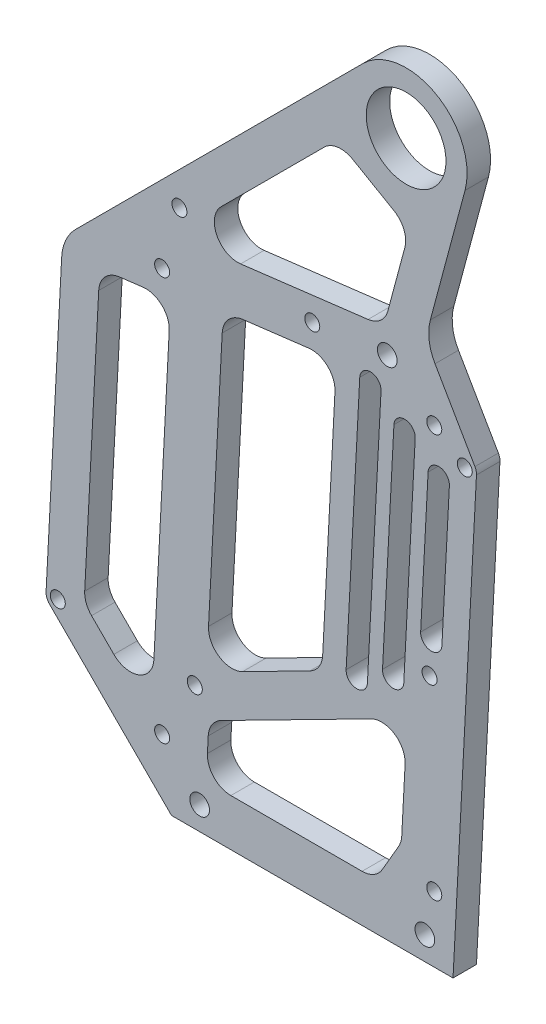
SolidWorks part; units mm, degrees
material "6061 Alloy"
ref_plane "Front Plane" through (0, 0, 0) normal (0, 0, 1) x (1, 0, 0)
ref_plane "Top Plane" through (0, 0, 0) normal (0, 1, 0) x (1, 0, 0)
ref_plane "Right Plane" through (0, 0, 0) normal (1, 0, 0) x (0, 0, -1)
sketch "Sketch1" plane through (0, 0, 0) normal (0, 0, 1) x (1, 0, 0)
  line L0 (0, 103.759) -> (0, -103.759) construction
  line L1 (-30, 76) -> (50, 76)
  line L2 (-30, 76) -> (-30, 256)
  line L3 (-30, 256) -> (50, 256)
  line L4 (50, 76) -> (50, 256)
  circle A0 centre (20, 226) radius 8.5
  dimension "D1" = 150
  dimension "D5" = 17
  dimension "D2" = 20
  dimension "D3" = 180
  dimension "D4" = 80
extrude "Boss-Extrude1" add sketch "Sketch1" along normal blind 5
sketch "Sketch2" plane through (0, 0, 5) normal (0, 0, 1) x (1, 0, 0)
  line L0 (20, 226) -> (20, 151) construction
  line L1 (20, 226) -> (-17.1819, 226) construction
  circle A0 centre (20, 151) radius 5.5
  dimension "D3" = 11
  dimension "D1" = 75
  dimension "D2" = 90
extrude "Cut-Extrude1" cut sketch "Sketch2" against normal blind 30
sketch "Sketch3" plane through (0, 0, 5) normal (0, 0, 1) x (1, 0, 0)
  circle A0 centre (0, 182) radius 1.6
  circle A1 centre (25, 129.3013) radius 1.6
  circle A2 centre (-25.0329, 102.5335) radius 1.6
  circle A3 centre (-15, 81) radius 2.5
  circle A4 centre (15, 81) radius 2.5
  circle A5 centre (24, 91) radius 2.5
  circle A6 centre (-24, 91) radius 2.5
  dimension "D1" = 5
  dimension "D2" = 3.2
extrude "Cut-Extrude2" cut sketch "Sketch3" against normal blind 5
sketch "Sketch4" plane through (0, 0, 5) normal (0, 0, 1) x (1, 0, 0)
  line L0 (10.8076, 235.1924) -> (-46.0411, 178.3437)
  line L1 (-46.0411, 178.3437) -> (-46.0411, 109.8941)
  line L2 (-46.0411, 109.8941) -> (-30, 76)
  line L3 (32.557, 222.6354) -> (22.7869, 186.1729)
  line L4 (22.7869, 186.1729) -> (30, 173.6795)
  line L5 (30, 173.6795) -> (30, 76)
  line L6 (-30, 76) -> (50, 76) construction
  line L7 (30, 76) -> (50, 76)
  line L8 (50, 76) -> (50, 256)
  line L9 (50, 256) -> (-30, 256)
  line L10 (-30, 256) -> (-68.6435, 166)
  line L11 (-68.6435, 166) -> (-57.2516, 84.4416)
  line L12 (-57.2516, 84.4416) -> (-30, 76)
  circle A0 centre (20, 226) radius 13
  circle A1 centre (20, 151) radius 5.5 construction
  line M14 (-30, 256) -> (-30, 76)
  line M15 (-30, 76) -> (50, 76)
  line M16 (50, 76) -> (50, 256)
  line M17 (50, 256) -> (-30, 256)
  dimension "D1" = 26
  dimension "D4" = 20
  dimension "D5" = 60
  dimension "D2" = 75
  dimension "D3" = 45
  dimension "D6" = 60
extrude "Cut-Extrude3" cut sketch "Sketch4" against normal blind 10 contours A0 L3 L4 L5 L0 M15 M16 M17 M14 region at (-10.989, 216.1814, 5)
sketch "Sketch5" plane through (0, 0, 5) normal (0, 0, 1) x (1, 0, 0)
  line L0 (-30, 194.3848) -> (-46.5355, 177.8492)
  line L1 (-48, 174.3137) -> (-48, 96.0711)
  line L2 (-46.5355, 92.5355) -> (-30, 76)
  line L4 (10.8076, 235.1924) -> (-30, 194.3848) construction
  line L6 (-30, 194.3848) -> (-30, 76) construction
  line L15 (-30, 76) -> (30, 76) construction
  line L16 (-35, 169.3848) -> (-35, 101) construction
  line L17 (-30, 169.3848) -> (-30, 101)
  line L18 (-40, 169.3848) -> (-40, 101)
  line L19 (-30, 138.6777) -> (-30, 121.7071)
  line L20 (-30, 138.6777) -> (-40, 148.6777)
  line L21 (-30, 121.7071) -> (-40, 131.7071)
  line L22 (-40, 148.6777) -> (-40, 131.7071)
  line L23 (-40, 148.6777) -> (-30, 121.7071)
  arc A0 (-30, 169.3848) -> (-40, 169.3848) centre (-35, 169.3848) ccw
  arc A1 (-40, 101) -> (-30, 101) centre (-35, 101) ccw
  arc A2 (-48, 96.0711) -> (-46.5355, 92.5355) centre (-43, 96.0711) ccw
  arc A3 (-46.5355, 177.8492) -> (-48, 174.3137) centre (-43, 174.3137) ccw
  point P14 (-35, 135.1924)
  point P26 (-48, 94)
  point P29 (-48, 176.3848)
  line M19 (-30, 194.3848) -> (-30, 76)
  dimension "D6" = 5
  dimension "D9" = 5
  dimension "D1" = 18
  dimension "D2" = 45
  dimension "D3" = 7
  dimension "D4" = 7
  dimension "D5" = 8
  dimension "D7" = 12
  dimension "D8" = 135
extrude "Boss-Extrude2" add sketch "Sketch5" against normal blind 5 contours L1 L2 L0 A1 L18 A0 L17 M19 | L16 L23 L18 L21 | L20 L16 L23 L17 | L16 L20 L23 | L23 L16 L21 region at (-40.982, 135.1924, 5) region at (-32.2222, 134.3002, 5) region at (-33.3333, 127.8689, 5) region at (-36.6667, 142.5159, 5) region at (-37.7778, 136.0845, 5)
fillet "Fillet1" radius 2 4 edges at (-40, 131.7071, 2.5) (-40, 148.6777, 2.5) (-30, 121.7071, 2.5) (-30, 138.6777, 2.5)
fillet "Fillet2" radius 5 2 edges at (30, 173.6795, 2.5) (22.7869, 186.1729, 2.5)
sketch "Sketch6" plane through (0, 0, 5) normal (0, 0, 1) x (1, 0, 0)
  line L0 (32.557, 222.6354) -> (23.323, 188.1734) construction
  line L1 (23.8225, 184.3793) -> (29.3301, 174.8397) construction
  circle A0 centre (15.9821, 183.9592) radius 2.1
  dimension "D1" = 4.2
  dimension "D2" = 6
  dimension "D3" = 7
extrude "Cut-Extrude4" cut sketch "Sketch6" against normal blind 5
sketch "Sketch7" plane through (0, 0, 0) normal (0, 0, -1) x (-1, 0, 0)
  line L1 (-30, 76) -> (28.3649, 76)
  line L2 (-30, 76) -> (-30, 95.1786)
  line L3 (-30, 95.1786) -> (28.3649, 95.1786)
  line L4 (28.3649, 76) -> (28.3649, 95.1786)
extrude "Boss-Extrude3" add sketch "Sketch7" against normal blind 5
sketch "Sketch8" plane through (0, 0, 0) normal (0, 0, -1) x (-1, 0, 0)
  circle A0 centre (24, 81) radius 2.1
  circle A1 centre (-24, 81) radius 2.1
extrude "Cut-Extrude5" cut sketch "Sketch8" against normal blind 5
sketch "Sketch9" plane through (0, 0, 0) normal (0, 0, -1) x (-1, 0, 0)
  circle A0 centre (-26, 176) radius 1.6
  circle A1 centre (32, 176) radius 1.6
  circle A2 centre (-26, 90) radius 1.6
  circle A3 centre (32, 90) radius 1.6
  dimension "D1" = 3.2
extrude "Cut-Extrude6" cut sketch "Sketch9" against normal blind 5
sketch "Sketch10" plane through (0, 0, 0) normal (0, 0, -1) x (-1, 0, 0)
  line L0 (-24.0903, 191.0371) -> (-35.0353, 172.0798)
  line L1 (-23.323, 188.1734) -> (-32.557, 222.6354) construction
  line L2 (-35.0353, 172.0798) -> (-30, 76)
  line L3 (-30, 76) -> (-30, 172.3397) construction
  line L4 (-29.3301, 174.8397) -> (-23.8225, 184.3793) construction
  line L5 (-22.7869, 186.1729) -> (-24.0903, 191.0371)
  line L6 (-29.3301, 174.8397) -> (-22.7869, 186.1729)
  line L7 (-30, 76) -> (-30, 172.3397)
  line L8 (30, 120.8787) -> (30, 101) construction
  line L9 (40, 126.8787) -> (40, 101) construction
  line L10 (30, 169.3848) -> (30, 101)
  line L11 (40, 169.3848) -> (40, 101)
  line L12 (46.5355, 92.5355) -> (56.7886, 102.7886)
  line L13 (56.7886, 102.7886) -> (53.2043, 171.1805)
  line L16 (46.5355, 92.5355) -> (30, 76) construction
  line L17 (53.2043, 171.1805) -> (46.5355, 177.8492)
  line L18 (46.5355, 177.8492) -> (46.5355, 92.5355)
  line L19 (46.5355, 177.8492) -> (-10.8076, 235.1924) construction
  circle A0 centre (-32.5, 171.4711) radius 1.6
  arc A1 (30, 101) -> (40, 101) centre (35, 101) ccw construction
  arc A2 (40, 169.3848) -> (30, 169.3848) centre (35, 169.3848) ccw construction
  arc A3 (30, 101) -> (40, 101) centre (35, 101) ccw
  arc A4 (40, 169.3848) -> (30, 169.3848) centre (35, 169.3848) ccw
  circle A5 centre (54.2338, 103.7693) radius 1.6
  circle A6 centre (-20, 151) radius 5.5 construction
  circle A7 centre (-20, 151) radius 5.5
  arc A8 (-29.3301, 174.8397) -> (-30, 172.3397) centre (-25, 172.3397) ccw construction
  arc A9 (-29.3301, 174.8397) -> (-30, 172.3397) centre (-25, 172.3397) ccw
  point P9 (46.5595, 92.5597)
  dimension "D3" = 3.2
  dimension "D4" = 2.5
  dimension "D5" = 2.5
  dimension "D2" = 2.5
  dimension "D6" = 2.5
  dimension "D7" = 2.5
  dimension "D8" = 3.2
  dimension "D1" = 3
  dimension "D9" = 14.5
extrude "Boss-Extrude4" add sketch "Sketch10" against normal blind 5
fillet "Fillet3" radius 10 2 edges at (-53.2043, 171.1805, 2.5) (24.0903, 191.0371, 2.5)
fillet "Fillet4" radius 2.5 2 edges at (35.0353, 172.0798, 2.5) (-56.7886, 102.7886, 2.5)
sketch "Sketch11" plane through (0, 0, 0) normal (0, 0, -1) x (-1, 0, 0)
  line L0 (50.49, 173.8948) -> (-10.8076, 235.1924) construction
  line L1 (30, 76) -> (-30, 76) construction
  line L2 (-20.7316, 209.4118) -> (-15.2369, 188.9052)
  line L3 (-15.2369, 188.9052) -> (29.6708, 183.4002)
  line L4 (-25.1624, 195.0381) -> (-32.557, 222.6354) construction
  line L5 (29.6708, 183.4002) -> (-5.2684, 218.3395)
  line L6 (-20, 226) -> (-13, 213.8756) construction
  line L7 (-5.2684, 218.3395) -> (-20.7316, 209.4118)
  line L8 (-26.9554, 166.612) -> (-25.3664, 136.2917) construction
  line L9 (-24.6885, 166.7308) -> (-23.0995, 136.4105)
  line L10 (-29.2223, 166.4932) -> (-27.6332, 136.1729)
  line L11 (-19.6723, 171.7117) -> (-17.2425, 125.3486) construction
  line L12 (-17.4054, 171.8305) -> (-14.9756, 125.4674)
  line L13 (-21.9392, 171.5929) -> (-19.5094, 125.2298)
  line L14 (-12.3892, 176.8114) -> (-9.485, 121.396) construction
  line L15 (-10.1223, 176.9302) -> (-7.2181, 121.5148)
  line L16 (-14.6561, 176.6926) -> (-11.7519, 121.2772)
  line L17 (-34.9966, 171.3403) -> (-30, 76) construction
  line L18 (-20.238, 119.0186) -> (-19.0075, 95.5379)
  line L19 (-19.0075, 95.5379) -> (-13.5007, 86)
  line L20 (-13.5007, 86) -> (22.6204, 86)
  line L21 (22.6204, 86) -> (22.0183, 97.4879)
  line L22 (22.0183, 97.4879) -> (-20.238, 119.0186)
  line L23 (30.1724, 171.1866) -> (45.2901, 169.3334)
  line L24 (45.2901, 169.3334) -> (48.6131, 105.9268)
  line L25 (48.6131, 105.9268) -> (34.3405, 91.6543)
  line L26 (34.3405, 91.6543) -> (30.1724, 171.1866)
  line L27 (-5.1502, 177.5939) -> (18.9765, 174.6363)
  line L28 (18.9765, 174.6363) -> (22.5637, 106.1887)
  line L30 (22.5637, 106.1887) -> (-2.0657, 118.738)
  line L31 (-2.0657, 118.738) -> (-5.1502, 177.5939)
  line L32 (56.7303, 103.9001) -> (53.4052, 167.3471) construction
  line L33 (56.0015, 102.0015) -> (30, 76) construction
  line L34 (-26.9554, 166.612) -> (-12.3892, 176.8114) construction
  line L35 (-26.1614, 187.4499) -> (-34.6651, 172.7211) construction
  line L36 (-17.2425, 125.3486) -> (-9.485, 121.396) construction
  circle A0 centre (28.3137, 189) radius 1.6
  circle A1 centre (-20, 226) radius 8.5 construction
  circle A2 centre (-15.9821, 183.9592) radius 2.1 construction
  circle A3 centre (0, 182) radius 1.6 construction
  arc A4 (-24.6885, 166.7308) -> (-29.2223, 166.4932) centre (-26.9554, 166.612) ccw
  arc A5 (-27.6332, 136.1729) -> (-23.0995, 136.4105) centre (-25.3664, 136.2917) ccw
  arc A6 (-17.4054, 171.8305) -> (-21.9392, 171.5929) centre (-19.6723, 171.7117) ccw
  arc A7 (-19.5094, 125.2298) -> (-14.9756, 125.4674) centre (-17.2425, 125.3486) ccw
  arc A8 (-10.1223, 176.9302) -> (-14.6561, 176.6926) centre (-12.3892, 176.8114) ccw
  arc A9 (-11.7519, 121.2772) -> (-7.2181, 121.5148) centre (-9.485, 121.396) ccw
  circle A10 centre (32, 176) radius 1.6 construction
  point P11 (-26.1609, 151.4519)
  point P24 (-18.4574, 148.5302)
  point P35 (-10.9371, 149.1037)
  point P44 (-25, 129.3013)
  point P58 (-21.9971, 120.504)
  point P64 (-25, 124.9113)
  point P65 (17.081, 88.8282)
  point P66 (-25, 98.5817)
  point P71 (23.347, 110.3501)
  point P72 (23.5789, 105.9268)
  point P73 (23.5789, 105.5185)
  point P76 (-20.7316, 94.4624)
  dimension "D1" = 3.2
  dimension "D2" = 5
  dimension "D7" = 5
  dimension "D8" = 5
  dimension "D9" = 2.27
  dimension "D3" = 113
  dimension "D4" = 14
  dimension "D5" = 8
  dimension "D6" = 8
  dimension "D10" = 7.54
  dimension "D11" = 7.54
  dimension "D12" = 10
  dimension "D13" = 5
  dimension "D14" = 8
  dimension "D15" = 8
  dimension "D16" = 11
  dimension "D17" = 5
  dimension "D18" = 25
  dimension "D19" = 60
  dimension "D20" = 15
  dimension "D21" = 5
  dimension "D22" = 8
  dimension "D23" = 12
  dimension "D24" = 12
  dimension "D25" = 7
  dimension "D26" = 8
  dimension "D27" = 7
  dimension "D28" = 60
  dimension "D29" = 5
extrude "Cut-Extrude7" cut sketch "Sketch11" against normal blind 5
fillet "Fillet5" radius 5 17 edges at (-48.6131, 105.9268, 2.5) (-22.5637, 106.1887, 2.5) (-34.3405, 91.6543, 2.5) (13.5007, 86, 2.5) (19.0075, 95.5379, 2.5) (2.0657, 118.738, 2.5) (-22.0183, 97.4879, 2.5) (-45.2901, 169.3334, 2.5) (-18.9765, 174.6363, 2.5) (20.238, 119.0186, 2.5) (-30.1724, 171.1866, 2.5) (5.1502, 177.5939, 2.5) (-29.6708, 183.4002, 2.5) (15.2369, 188.9052, 2.5) (5.2684, 218.3395, 2.5) (20.7316, 209.4118, 2.5) (-22.6204, 86, 2.5)
